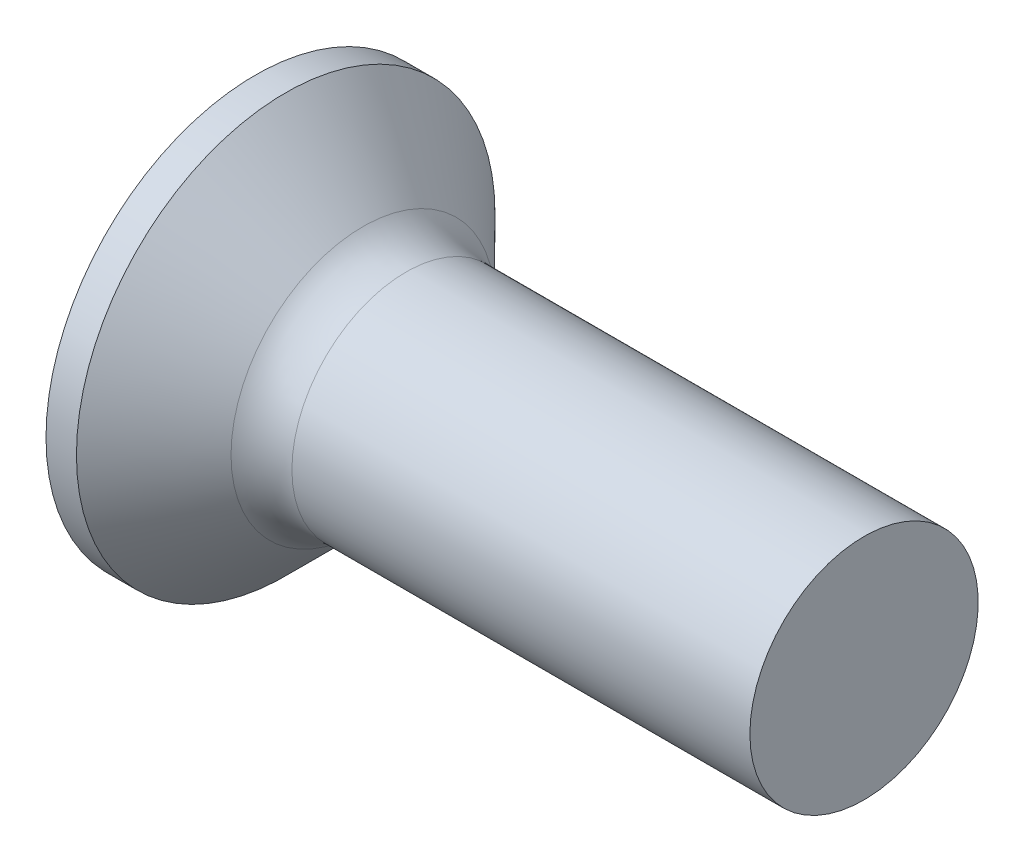
SolidWorks part; units mm, degrees
revolve "Base-Revolve" add sketch "BodySke" angle 360 about L5 other way angle 60
sketch "BodySke" plane through (0, 0, 0) normal (0, 0, 1) x (1, 0, 0)
  line L0 (0, 0) -> (0, 2.75)
  line L1 (0, 2.75) -> (0.4, 2.75)
  line L2 (1.65, 1.5) -> (8, 1.5)
  line L3 (8, 1.5) -> (8, 0)
  line L4 (8, 0) -> (0, 0)
  line L5 (-6.35, 0) -> (82.55, 0) construction
  line L6 (1.65, -1.5) -> (8, -1.5) construction
  line L7 (0.4, -2.75) -> (1.65, -1.5) construction
  line L8 (0.4, 2.75) -> (1.65, 1.5)
  line L9 (0, -2.75) -> (0.4, -2.75) construction
  line L10 (2.15, 3.0875) -> (2.15, -6.4375) construction
  line L11 (0, 6.35) -> (0, -3.175) construction
  dimension "Diameter" = 3
  dimension "D6" = 0.4
cosmetic thread "ThreadCosmetic" [suppressed] parameters "Thread_length"=5.85, "Thread_minor"=2.439
ref_plane "Plane1" through (0, 0, 0) normal (0, 0, 1) x (1, 0, 0)
ref_plane "Plane2" through (0, 0, 0) normal (0, 1, 0) x (1, 0, 0)
ref_plane "Plane3" through (0, 0, 0) normal (1, 0, 0) x (0, 0, -1)
fillet "Fillet1" radius 0.8 1 edges at (1.65, 0, 1.5)
sketch "Sketch3" plane through (0, 0, 0) normal (-1, 0, 0) x (0, 0, 1)
  line L0 (-0.37, 1.5) -> (0.37, 1.5)
  line L1 (0.37, 1.5) -> (0.37, -1.5)
  line L2 (0.37, -1.5) -> (-0.37, -1.5)
  line L3 (-0.37, -1.5) -> (-0.37, 1.5)
  dimension "Cross_dia" = 3
  dimension "Cross_width" = 0.74
  dimension "D1" = 1.5
  dimension "D2" = 0.37
ref_plane "Plane4" through (2.01, 0, 0) normal (-1, 0, 0) x (0, 0, 1)
sketch "Sketch4" plane through (2.01, 0, 0) normal (-1, 0, 0) x (0, 0, 1)
  line L0 (-0.37, 0.4979) -> (0.37, 0.4979)
  line L3 (0.37, 0.4979) -> (0.37, -0.4979)
  line L4 (0.37, -0.4979) -> (-0.37, -0.4979)
  line L5 (-0.37, -0.4979) -> (-0.37, 0.4979)
  dimension "D2" = 0.9957
  dimension "D1" = 0.74
  dimension "D4" = 0.4979
  dimension "D3" = 0.37
loft "Recess" cut profiles "Sketch3", "Sketch4"
pattern_circular "RecPat" count 2 every 90 about axis through (-6.35, 0, 0) along (1, 0, 0) of "Recess"
sketch "RecCorSke" plane through (0, 0, 0) normal (0, 0, 1) x (1, 0, 0)
  line L0 (-3.175, 0) -> (15.875, 0) construction
  line L2 (0, 0) -> (0, 0.6966)
  line L3 (0, 0.6966) -> (2.01, 0.556)
  line L4 (2.01, 0.556) -> (2.1907, 0)
  line L5 (2.1907, 0) -> (0, 0)
revolve "RecessCore" cut sketch "RecCorSke" angle 360 about L0
equation "\"D1@Sketch3\" = \"Cross_dia@Sketch3\" / 2"
equation "\"D2@Sketch3\" = \"Cross_width@Sketch3\" / 2"
equation "\"Depth@RecCorSke\" = \"Cross_depth@Plane4\""
equation "\"D1@Sketch4\" = \"Cross_width@Sketch3\""
equation "\"D2@Sketch4\" = \"Cross_dia@Sketch3\" - 2.0 * \"Cross_depth@Plane4\" * tan(26.5  * 0.017453292)"
equation "\"D3@Sketch4\" = \"D1@Sketch4\" / 2"
equation "\"D4@Sketch4\" = \"D2@Sketch4\" / 2"
equation "\"Thread_length@ThreadCosmetic\" = ((sgn( (\"Length@BodySke\" - \"Advance@BodySke\" * 1.0 - \"Head_ht@BodySke\" ) - \"Thread_nom@BodySke\" )-1)*( (\"Length@BodySke\" - \"Advance@BodySke\" * 1.0 - \"Head_ht@BodySke\" ) - \"Thread_nom@BodySke\" ))/-2+ \"Thread_nom@BodySke\""
equation "\"Thread_minor@ThdSchSke\" = \"Thread_minor@ThreadCosmetic\""
equation "\"Diameter@ThdSchSke\" = \"Diameter@BodySke\""
equation "\"Overcut@ThdSchSke\" = \"Diameter@BodySke\" * 1.25"
equation "\"Start@ThdSchSke\" = 0.000001 + \"Length@BodySke\" - \"Thread_length@ThreadCosmetic\"  '---Countersunk---"
equation "\"Num_threads@ThdSchPat\" = int( \"Thread_length@ThreadCosmetic\" / \"Advance@BodySke\" + 0.999 )  + 1"
equation "\"Advance@ThdSchPat\" = \"Thread_length@ThreadCosmetic\" /  (\"Num_threads@ThdSchPat\" - 1) 'relax it"
